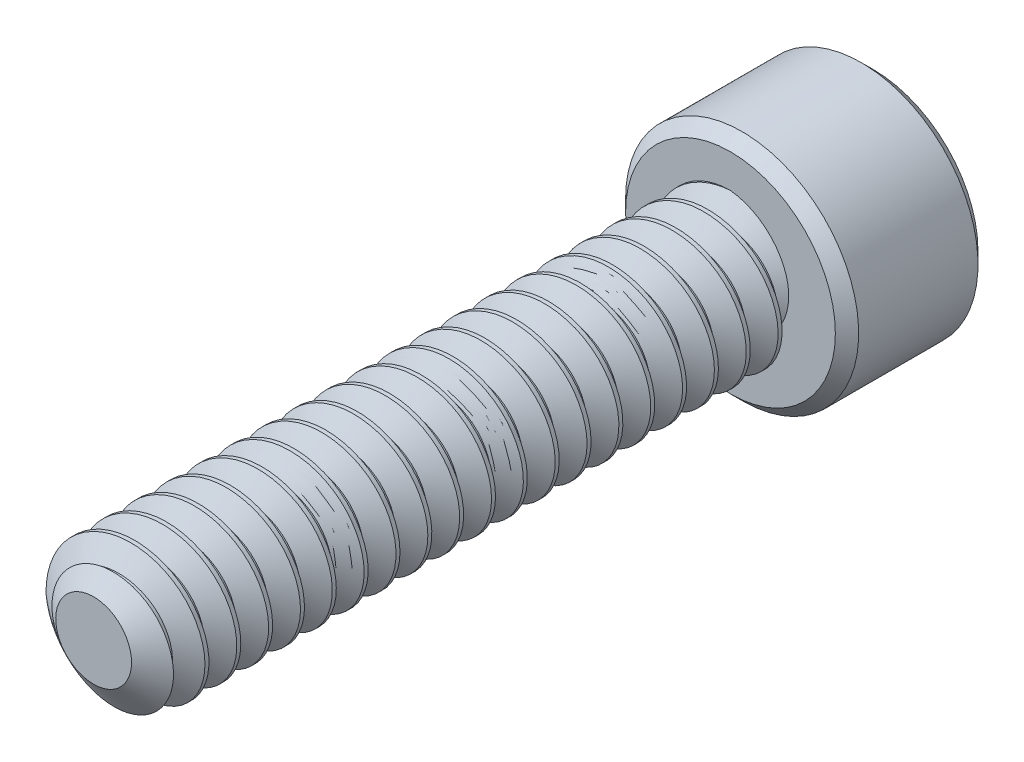
SolidWorks part; units mm, degrees
other "DetailItem1"
ref_plane "Front Plane" through (0, 0, 0) normal (0, 0, 1) x (1, 0, 0)
ref_plane "Top Plane" through (0, 0, 0) normal (0, 1, 0) x (1, 0, 0)
ref_plane "Right Plane" through (0, 0, 0) normal (1, 0, 0) x (0, 0, -1)
sketch "Sketch1" plane through (0, 0, 0) normal (0, 0, 1) x (1, 0, 0)
  circle A0 centre (0, 0) radius 1.4224
  dimension "OD" = 2.8448
extrude "Extrude1" add sketch "Sketch1" against normal blind 12.7
sketch "Sketch2" plane through (0, 0, 0) normal (0, 0, 1) x (1, 0, 0)
  circle A0 centre (0, 0) radius 1.4224 construction
  circle A1 centre (0, 0) radius 1.4224
curve "Helix/Spiral1" pitch 0.635 height 13.335 radius 1.4224 centre (0, 0, 0) axis (0, 0, -1) start towards (0, 1, 0) parameters "pitch"=0.635
sketch "Sketch3" plane through (0, 0, 0) normal (1, 0, 0) x (0, 0, -1)
  line L0 (-0.5556, 1.4224) -> (-0.3175, 1.01)
  line L1 (-0.3175, 1.01) -> (-0.2381, 1.01)
  line L2 (-0.2381, 1.01) -> (0, 1.4224)
  line L3 (-0.5556, 1.4224) -> (0, 1.4224)
  line L4 (-0.2778, 1.4224) -> (-0.2778, 1.01) construction
  line L5 (-0.4366, 1.2162) -> (-0.1191, 1.2162) construction
  line L6 (0, 1.4224) -> (0, -1.4224) construction
  dimension "D1" = 0.0794
  dimension "D2" = 0.3175
  dimension "D3" = 60
sweep "Cut-Sweep1" cut profiles "Sketch3" path "Helix/Spiral1" align with end faces yes
sketch "Sketch4" plane through (0, 0, 0) normal (1, 0, 0) x (0, 0, -1)
  line L0 (0.4666, 1.4224) -> (0, 0.756)
  line L1 (0, 0.756) -> (0, 1.4224)
  line L2 (0.4666, 1.4224) -> (0, 1.4224)
  line L3 (-0.5556, 1.4224) -> (0, 1.4224) construction
  line L4 (0, 0) -> (7.0209, 0) construction
  dimension "D1" = 55
  dimension "D2" = 0.254
revolve "Cut-Revolve1" cut sketch "Sketch4" angle 360 about L4
sketch "Sketch6" plane through (0, 0, -12.7) normal (0, 0, -1) x (-1, 0, 0)
  circle A0 centre (0, 0) radius 2.3241
  dimension "head dia" = 4.6482
extrude "Extrude2" add sketch "Sketch6" along normal blind 2.8448
sketch "Sketch7" plane through (0, 0, -15.5448) normal (0, 0, -1) x (-1, 0, 0)
  line L1 (0, 1.3748) -> (-1.1906, 0.6874)
  line L2 (-1.1906, 0.6874) -> (-1.1906, -0.6874)
  line L3 (-1.1906, -0.6874) -> (0, -1.3748)
  line L4 (0, -1.3748) -> (1.1906, -0.6874)
  line L5 (1.1906, -0.6874) -> (1.1906, 0.6874)
  line L6 (1.1906, 0.6874) -> (0, 1.3748)
  circle A0 centre (0, 0) radius 1.1906 construction
  dimension "hex dia" = 2.3813
extrude "Cut-Extrude1" cut sketch "Sketch7" against normal blind 1.7859
sketch "Sketch8" plane through (0, 0, -15.5448) normal (0, 0, -1) x (-1, 0, 0)
  circle A0 centre (0, 0) radius 1.3748
extrude "Cut-Extrude2" cut sketch "Sketch8" against normal through all draft 45
chamfer "Chamfer1" distance 0.2324 angle 45 2 edges at (-2.3241, 0, -15.5448) (-2.3241, 0, -12.7)
sketch "Sketch10" plane through (0, 0, -12.7) normal (0, 0, 1) x (1, 0, 0)
  circle A1 centre (0, 0) radius 1.4224
  circle A2 centre (0, 0) radius 1.4224
  dimension "D1" = 0
ref_plane "Plane1" through (0, 0, -19.05) normal (0, 0, 1) x (1, 0, 0)
extrude "partial thread" [suppressed] add sketch "Sketch10" along normal up to surface (31.75 mm away) separate body up to plane "Plane1"
chamfer "Chamfer2" [suppressed] distance 0.0569 angle 45
combine bodies "Combine1" [suppressed] operation type add bodies to combine 107 108
sketch "Sketch9" plane through (0, 0, 0) normal (1, 0, 0) x (0, 0, -1)
  line L0 (0, 1.4224) -> (0, -1.4224) construction
  line L1 (1.5875, 1.4224) -> (1.5875, -1.4224) construction
  dimension "D1" = 1.5875
equation "\"D3@Helix/Spiral1\" = \"screw length@Extrude1\"+\"pitch@Helix/Spiral1\""
equation "\"D1@Sketch3\" = \"pitch@Helix/Spiral1\"*.125"
equation "\"D2@Sketch3\" = \"pitch@Helix/Spiral1\"*.5"
equation "\"D1@Cut-Extrude1\" = \"hex dia@Sketch7\"*.75"
equation "\"D1@Chamfer1\" = \"head dia@Sketch6\"*.05"
equation "\"D1@Sketch9\" = \"pitch@Helix/Spiral1\"*2.5"
equation "\"D1@Chamfer2\"=\"OD@Sketch1\"*.02"
